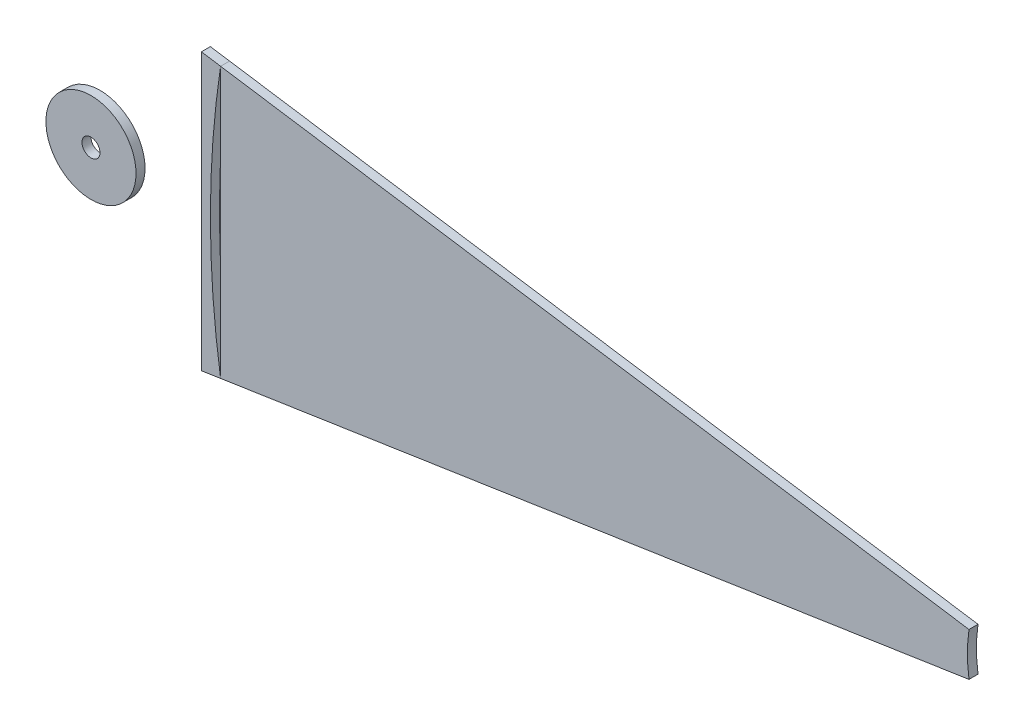
SolidWorks part; units mm, degrees
ref_plane "Front Plane" through (0, 0, 0) normal (0, 0, 1) x (1, 0, 0)
ref_plane "Top Plane" through (0, 0, 0) normal (0, 1, 0) x (1, 0, 0)
ref_plane "Right Plane" through (0, 0, 0) normal (1, 0, 0) x (0, 0, -1)
sketch "Sketch1" plane through (0, 0, 0) normal (0, 0, 1) x (1, 0, 0)
  line L1 (0, 0) -> (-98.8686, 15)
  line L2 (-98.8686, 15) -> (-98.8686, -15)
  line L3 (-98.8686, -15) -> (0, 0)
  line L4 (-98.8686, 15) -> (-101, 15.3234)
  line L5 (-101, 15.3234) -> (-101, -15.3234)
  line L6 (-101, -15.3234) -> (-98.8686, -15)
  circle A2 centre (0, 0) radius 100
  circle A3 centre (0, 0) radius 101
  circle A6 centre (0, 0) radius 16
  dimension "D2" = 200
  dimension "D3" = 1
  dimension "D4" = 32
  dimension "D1" = 30
extrude "Boss-Extrude1" add sketch "Sketch1" along normal blind 0.5 and the other way blind 0.5 contours A6 L1 L2 L3 | A3 L4 L5 | A3 L5 L6 | L4 A3 L6 A2 region at (-67.3877, 0, 0) region at (-100.1215, 0, 0) region at (-100.6569, 11.4318, 0) region at (-100.6569, -11.4318, 0)
sketch "Sketch2" plane through (0, 0, 0) normal (0, 0, 1) x (1, 0, 0)
  line L0 (-113.25, 0) -> (0, 0) construction
  circle A0 centre (-113.25, 0) radius 1
  circle A5 centre (-113.25, 0) radius 5
  dimension "D1" = 2
  dimension "D3" = 10
  dimension "D2" = 113.25
extrude "Boss-Extrude2" add sketch "Sketch2" along normal blind 0.5 and the other way blind 0.5 separate body
